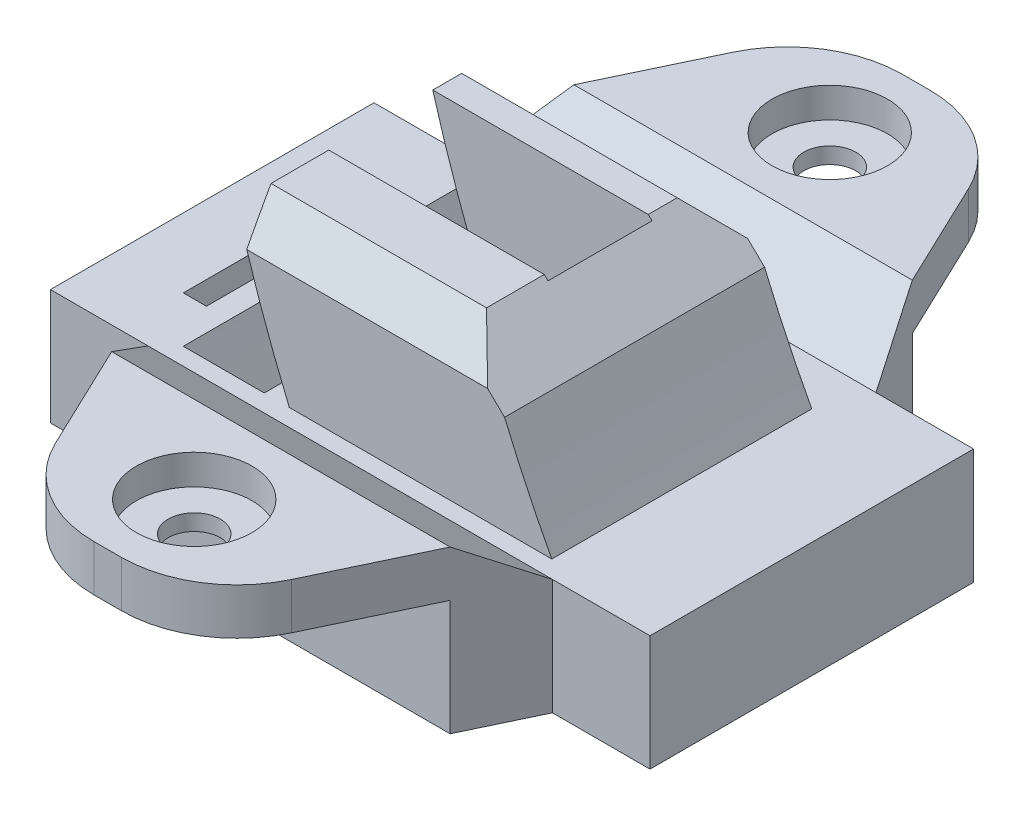
SolidWorks part; units mm, degrees
note: The reader was unsure of these and kept them because the rebuilt part matched: shared geometry of "Schizzo3<3>", "Schizzo3<4>".
material "ABS"
ref_plane "Piano frontale" through (0, 0, 0) normal (0, 0, 1) x (1, 0, 0)
ref_plane "Piano superiore" through (0, 0, 0) normal (0, 1, 0) x (1, 0, 0)
ref_plane "Piano destro" through (0, 0, 0) normal (1, 0, 0) x (0, 0, -1)
sketch "Schizzo2" plane through (0, 0, 0) normal (0, 1, 0) x (1, 0, 0)
  line L0 (0, 0) -> (0, 20) construction
  line L1 (-125, 20) -> (125, 20) construction
  line L2 (-125, 20) -> (-125, -20) construction
  line L3 (-125, -20) -> (125, -20) construction
  line L4 (125, 20) -> (125, -20) construction
  line L5 (0, 0) -> (125, 0) construction
  line L6 (-123.253, 20) -> (-123.253, -20)
  line L7 (-71.3649, 20) -> (-71.3649, -20)
  line L8 (-123.253, 20) -> (-71.3649, 20)
  line L9 (-123.253, -20) -> (-71.3649, -20)
  dimension "D1" = 40
  dimension "D2" = 250
  dimension "D3" = 123.253
  dimension "D4" = 51.8881
extrude "Estrusione-Estrusione2" add sketch "Schizzo2" against normal blind 10 contours L1 L6 L3 L4
sketch "Schizzo3" plane through (0, 0, 0) normal (0, 0, 1) x (1, 0, 0)
  line L0 (0, 0) -> (0, 44) construction
  circle A0 centre (0, 44) radius 121.5
  circle A1 centre (0, 44) radius 115
  circle A2 centre (0, 44) radius 113
  circle A3 centre (0, 44) radius 105
  circle A4 centre (0, 44) radius 95
  circle A5 centre (0, 44) radius 92.5
  point P2 (0, 0)
  dimension "D2" = 243
  dimension "D3" = 230
  dimension "D4" = 2
  dimension "D5" = 210
  dimension "D6" = 10
  dimension "D7" = 185
  dimension "D1" = 44
extrude "Estrusione-Estrusione3" add sketch "Schizzo3" along normal blind 12.5 and the other way blind 10 contours A4 A5 | A3 A4 | A2 A3
extrude "Taglio-Estrusione1" cut sketch "Schizzo3<3>" against normal blind 4.5 and the other way blind 4.5 contours A3 A4 | A2 A3 | A1 A2
sketch "Schizzo3<3>" plane through (0, 0, 0) normal (0, 0, 1) x (1, 0, 0) same geometry as "Schizzo3"
extrude "Taglio-Estrusione2" cut sketch "Schizzo3<4>" against normal blind 12.5 and the other way blind 12.5 contours A0 A1
sketch "Schizzo3<4>" plane through (0, 0, 0) normal (0, 0, 1) x (1, 0, 0) same geometry as "Schizzo3"
sketch "Schizzo4" plane through (0, 0, 12.5) normal (0, 0, 1) x (1, 0, 0)
  line L0 (150, 13) -> (150, -10)
  line L1 (-150, 163) -> (150, 163)
  line L2 (-150, 163) -> (-150, 13)
  line L3 (-150, 13) -> (0, 13)
  line L4 (150, 163) -> (150, 13)
  line L5 (-150, -10) -> (0, -10)
  line L6 (-150, -10) -> (-150, -80)
  line L7 (-150, -80) -> (150, -80)
  line L8 (150, -10) -> (150, -80)
  line L9 (0, 13) -> (0, -10)
  dimension "D1" = 13
  dimension "D2" = 23
  dimension "D3" = 70
  dimension "D4" = 150
  dimension "D5" = 300
  dimension "D6" = 150
extrude "Taglio-Estrusione3" cut sketch "Schizzo4" against normal blind 79.5 and the other way blind 79.5
chamfer "Smusso1" distance 3 angle 45 3 edges at (-97.9077, 13, -10) (-87.1507, 13, 1.25) (-97.9077, 13, 12.5)
sketch "Schizzo7" plane through (-71.3649, 0, 0) normal (1, 0, 0) x (0, 0, -1)
  line L0 (-20, 0) -> (-35, 0)
  line L1 (-35, 0) -> (-35, 4)
  line L2 (-35, 4) -> (-20, 4)
  line L3 (-20, 4) -> (-14, 0)
  line L4 (20, 0) -> (-20, 0) construction
  line L5 (-20, 0) -> (-14, 0)
  line L6 (-20, 4) -> (-20, 0) construction
  line L7 (20, 0) -> (20, 4) construction
  line L8 (20, 4) -> (35, 4)
  line L9 (35, 4) -> (35, 0)
  line L10 (35, 0) -> (20, 0)
  line L11 (20, 0) -> (14, 0)
  line L12 (14, 0) -> (20, 4)
  dimension "D1" = 15
  dimension "D2" = 4
  dimension "D3" = 6
extrude "Estrusione-Estrusione5" add sketch "Schizzo7" against normal up to vertex (51.8881 mm away) up to point (-123.253, 0, -20)
sketch "Schizzo8" plane through (0, 4, 0) normal (0, 1, 0) x (1, 0, 0)
  line L0 (-97.309, 27.5) -> (-97.309, -27.5) construction
  line L1 (-123.253, 14) -> (-123.253, -14) construction
  line L2 (-123.253, -20) -> (-71.3649, -20) construction
  line L3 (-123.253, 20) -> (-71.3649, 20) construction
  point P0 (-97.309, -27.5)
  point P2 (-97.309, 27.5)
  dimension "D1" = 25.9441
  dimension "D2" = 7.5
  dimension "D3" = 7.5
hole_wizard "Foro lamato per Vite M4 a testa cilindrica piana-1" positions "Schizzo8" profile "Schizzo9" counterbore size "M4" standard "ISO"
sketch "Schizzo9" plane through (-97.309, 4, 27.5) normal (1, 0, 0) x (0, 0, 1)
  line L0 (0, 0) -> (0, 31.3519)
  line L1 (0, 31.3519) -> (2.25, 30)
  line L2 (2.25, 30) -> (2.25, 2.6)
  line L3 (2.25, 2.6) -> (5, 2.6)
  line L4 (5, 2.6) -> (5, 0)
  line L5 (5, 0) -> (0, 0)
  line L10 (0, 31.3519) -> (-2.25, 30) construction
  line L11 (0, -6.35) -> (0, 107.95) construction
  dimension "Hole Dia." = 4.5
  dimension "Hole Depth" = 30
  dimension "C'Bore Dia." = 10
  dimension "C'Bore Depth" = 2.6
  dimension "Drill Angle" = 118
sketch "Schizzo10" plane through (0, 0, 0) normal (0, 1, 0) x (1, 0, 0)
  line L1 (-117.253, 8.5) -> (-115.253, 8.5)
  line L2 (-117.253, 8.5) -> (-117.253, -8.5)
  line L3 (-117.253, -8.5) -> (-115.253, -8.5)
  line L4 (-115.253, 8.5) -> (-115.253, -8.5)
  line L5 (-123.253, 0) -> (-117.253, 0) construction
  line L6 (-123.253, 14) -> (-123.253, -14) construction
  line L7 (-113.253, -12.5) -> (-113.253, 12.5) construction
  point P12 (-117.253, 0)
  dimension "D1" = 17
  dimension "D2" = 2
  dimension "D3" = 2
extrude "Taglio-Estrusione4" cut sketch "Schizzo10" against normal blind 10
sketch "Schizzo11" plane through (0, 4, 0) normal (0, 1, 0) x (1, 0, 0)
  line L0 (-123.253, 14) -> (-123.253, 35)
  line L1 (-123.253, 35) -> (-104.809, 35)
  line L2 (-123.253, 35) -> (-71.3649, 35) construction
  line L3 (-104.809, 35) -> (-114.809, 14)
  line L4 (-123.253, 14) -> (-71.3649, 14) construction
  line L5 (-114.809, 14) -> (-123.253, 14)
  line L6 (-89.809, 35) -> (-71.3649, 35)
  line L7 (-71.3649, 35) -> (-71.3649, 14)
  line L8 (-71.3649, 14) -> (-79.809, 14)
  line L9 (-79.809, 14) -> (-89.809, 35)
  line L10 (-123.253, -14) -> (-123.253, -35)
  line L11 (-123.253, -35) -> (-104.809, -35)
  line L12 (-123.253, -35) -> (-71.3649, -35) construction
  line L13 (-104.809, -35) -> (-114.809, -14)
  line L14 (-123.253, -14) -> (-71.3649, -14) construction
  line L15 (-114.809, -14) -> (-123.253, -14)
  line L16 (-89.809, -35) -> (-71.3649, -35)
  line L17 (-71.3649, -35) -> (-71.3649, -14)
  line L18 (-71.3649, -14) -> (-79.809, -14)
  line L19 (-79.809, -14) -> (-89.809, -35)
  dimension "D1" = 15
  dimension "D2" = 35
extrude "Taglio-Estrusione5" cut sketch "Schizzo11" against normal blind 33
fillet "Raccordo1" radius 10 4 edges at (-104.809, 2, -35) (-89.809, 2, -35) (-89.809, 2, 35) (-104.809, 2, 35)
